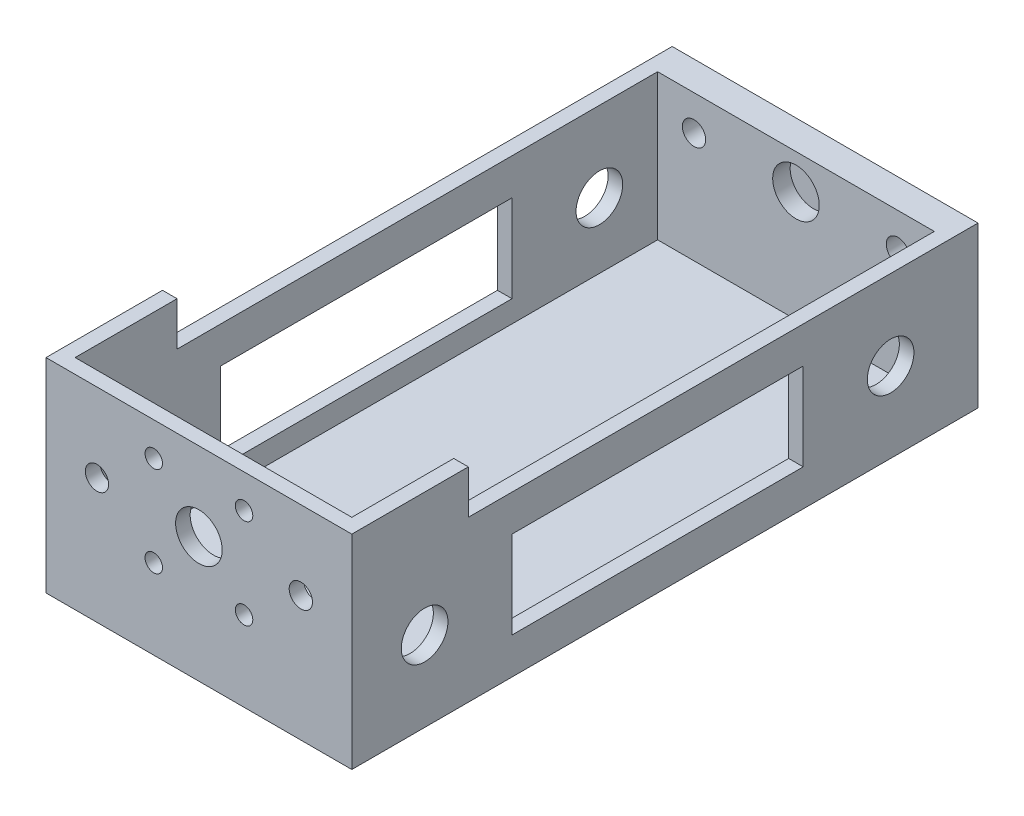
SolidWorks part; units mm, degrees
ref_plane "Front Plane" through (0, 0, 0) normal (0, 0, 1) x (1, 0, 0)
ref_plane "Top Plane" through (0, 0, 0) normal (0, 1, 0) x (1, 0, 0)
ref_plane "Right Plane" through (0, 0, 0) normal (1, 0, 0) x (0, 0, -1)
sketch "Sketch1" plane through (0, 0, 0) normal (0, 1, 0) x (1, 0, 0)
  line L1 (-50, 100) -> (50, 100)
  line L2 (-50, 100) -> (-50, -100)
  line L3 (-50, -100) -> (50, -100)
  line L4 (50, 100) -> (50, -100)
  line L5 (-50, 100) -> (50, -100) construction
  line L6 (-50, -100) -> (50, 100) construction
  point P0 (0, 0)
  dimension "D1" = 200
  dimension "D2" = 100
extrude "Boss-Extrude1" add sketch "Sketch1" along normal mid plane 5
sketch "Sketch2" plane through (-50, 0, 0) normal (-1, 0, 0) x (0, 0, 1)
  line L0 (100, 2.5) -> (100, -2.5) construction
  line L1 (-100, -2.5) -> (100, -2.5)
  line L2 (-100, -2.5) -> (-100, 67.5)
  line L3 (-100, 67.5) -> (100, 67.5)
  line L4 (100, -2.5) -> (100, 67.5)
  dimension "D1" = 70
extrude "Boss-Extrude2" add sketch "Sketch2" along normal mid plane 5
sketch "Sketch3" plane through (-52.5, 0, 0) normal (-1, 0, 0) x (0, 0, 1)
  line L0 (0, -2.5) -> (0, 67.5) construction
  line L1 (-100, -2.5) -> (100, -2.5) construction
  line L2 (100, 67.5) -> (-100, 67.5) construction
  circle A0 centre (-80, 25) radius 8
  circle A1 centre (80, 25) radius 8
  dimension "D3" = 16
  dimension "D1" = 80
  dimension "D2" = 25
extrude "Cut-Extrude1" cut sketch "Sketch3" against normal up to surface (5 mm away) up to face at (-47.5, 35, 0)
mirror "Mirror1" about plane through (0, 0, 0) normal (1, 0, 0) of "Boss-Extrude2", "Cut-Extrude1"
sketch "Sketch4" plane through (0, 0, -100) normal (0, 0, -1) x (-1, 0, 0)
  line L1 (-52.5, 67.5) -> (52.5, 67.5)
  line L2 (-52.5, 67.5) -> (-52.5, -2.5)
  line L3 (-52.5, -2.5) -> (52.5, -2.5)
  line L4 (52.5, 67.5) -> (52.5, -2.5)
extrude "Boss-Extrude3" add sketch "Sketch4" along normal blind 10
sketch "Sketch5" plane through (0, 0, 100) normal (0, 0, 1) x (1, 0, 0)
  line L1 (-52.5, 67.5) -> (52.5, 67.5)
  line L2 (-52.5, 67.5) -> (-52.5, -2.5)
  line L3 (-52.5, -2.5) -> (52.5, -2.5)
  line L4 (52.5, 67.5) -> (52.5, -2.5)
extrude "Boss-Extrude4" add sketch "Sketch5" along normal blind 5
sketch "Sketch6" plane through (-52.5, 0, 0) normal (-1, 0, 0) x (0, 0, 1)
  line L0 (0, 0) -> (0, 10) construction
  line L5 (-50, 40) -> (50, 40)
  line L6 (-50, 40) -> (-50, 10)
  line L7 (-50, 10) -> (50, 10)
  line L8 (50, 40) -> (50, 10)
  dimension "D1" = 10
  dimension "D2" = 30
  dimension "D3" = 100
extrude "Cut-Extrude2" cut sketch "Sketch6" against normal through all
sketch "Sketch7" plane through (0, 0, 105) normal (0, 0, -1) x (-1, 0, 0)
  line L0 (0, 40.5) -> (0, 0) construction
  line L1 (-15.5, 56) -> (15.5, 56) construction
  line L2 (-15.5, 56) -> (-15.5, 25) construction
  line L3 (-15.5, 25) -> (15.5, 25) construction
  line L4 (15.5, 56) -> (15.5, 25) construction
  line L5 (-15.5, 56) -> (15.5, 25) construction
  line L6 (-15.5, 25) -> (15.5, 56) construction
  circle A0 centre (-15.5, 56) radius 3
  circle A1 centre (-15.5, 25) radius 3
  circle A2 centre (15.5, 56) radius 3
  circle A3 centre (15.5, 25) radius 3
  circle A4 centre (0, 40.5) radius 8
  circle A5 centre (-35, 40.5) radius 4
  circle A6 centre (35, 40.5) radius 4
  point P0 (0, 40.5)
  dimension "D4" = 6
  dimension "D5" = 16
  dimension "D6" = 8
  dimension "D1" = 31
  dimension "D2" = 31
  dimension "D3" = 25
  dimension "D7" = 35
extrude "Cut-Extrude5" cut sketch "Sketch7" along normal through all contours A6 | A5 region at (35, 40.5, 105) region at (-35, 40.5, 105)
extrude "Cut-Extrude6" cut sketch "Sketch7<5>" along normal up to surface (5 mm away) contours A2 | A0 | A3 | A1 | A4 region at (15.5, 56, 105) region at (15.5, 25, 105) region at (-15.5, 56, 105) region at (-15.5, 25, 105) region at (0, 40.5, 105) up to face at (0, 35, 100)
sketch "Sketch7<5>" plane through (0, 0, 105) normal (0, 0, -1) x (-1, 0, 0) same geometry as "Sketch7"
sketch "Sketch8" plane through (0, 0, -100) normal (0, 0, -1) x (-1, 0, 0)
  circle A0 centre (0, 40.5) radius 8 construction
  circle A1 centre (0, 40.5) radius 8
extrude "Cut-Extrude7" cut sketch "Sketch8" along normal blind 6
sketch "Sketch9" plane through (0, 67.5, 0) normal (0, 1, 0) x (1, 0, 0)
  line L0 (-52.5, -65) -> (52.5, -65)
  line L1 (-52.5, -105) -> (-52.5, 110) construction
  line L3 (0, -38.5) -> (0, 38.5) construction
  line L4 (52.5, -105) -> (-52.5, -105) construction
  line L10 (-52.5, -105) -> (52.5, -105)
  line L11 (52.5, -105) -> (52.5, 110)
  line L12 (52.5, 110) -> (-52.5, 110)
  line L13 (-52.5, 110) -> (-52.5, -105)
  line L15 (52.5, -65) -> (52.5, 110)
  line L16 (52.5, 110) -> (-52.5, 110)
  line L17 (-52.5, 110) -> (-52.5, -65)
  dimension "D1" = 40
  dimension "D2" = 0
extrude "Cut-Extrude8" cut sketch "Sketch9" against normal blind 15
